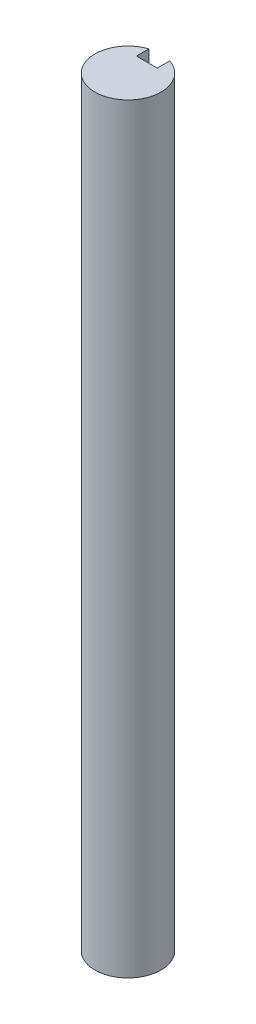
SolidWorks part; units mm, degrees
material "1023 Carbon Steel Sheet (SS)"
ref_plane "Front Plane" through (0, 0, 0) normal (0, 0, 1) x (1, 0, 0)
ref_plane "Top Plane" through (0, 0, 0) normal (0, 1, 0) x (1, 0, 0)
ref_plane "Right Plane" through (0, 0, 0) normal (1, 0, 0) x (0, 0, -1)
sketch "Sketch1" plane through (0, 0, 0) normal (0, 1, 0) x (1, 0, 0)
  line L0 (-1, 3.0134) -> (-1, 1.8134)
  line L1 (-1, 1.8134) -> (1, 1.8134)
  line L2 (1, 1.8134) -> (1, 3.0134)
  arc A0 (-1, 3.0134) -> (1, 3.0134) centre (0, 0) ccw
  point P5 (0, 1.8134)
  dimension "D1" = 6.35
  dimension "D2" = 2
  dimension "D3" = 1.2
extrude "Boss-Extrude1" add sketch "Sketch1" along normal blind 73.025
